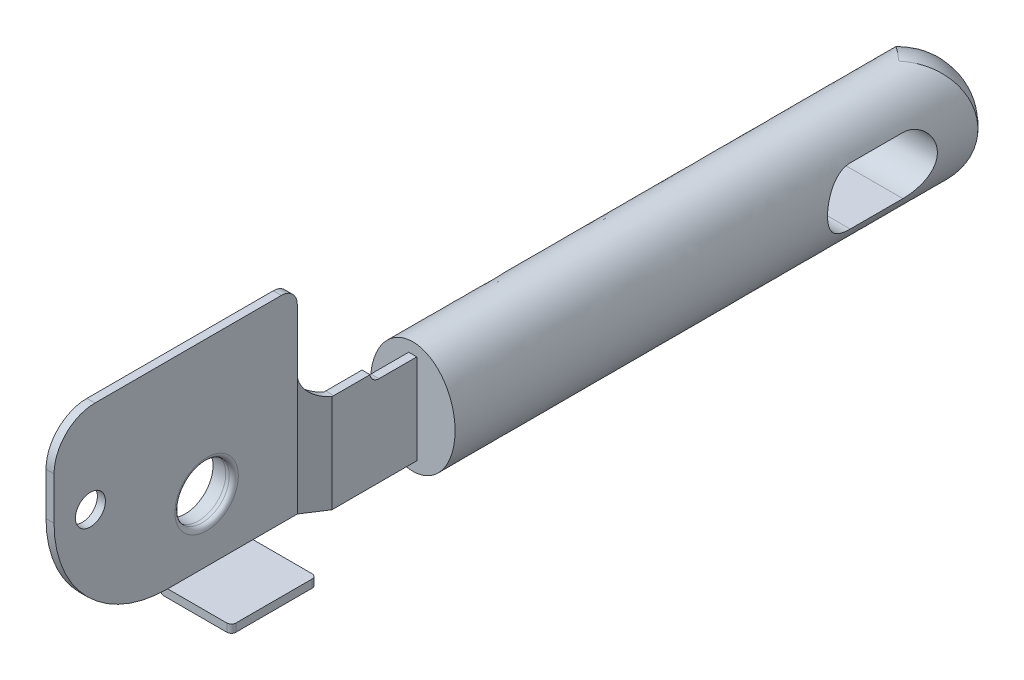
SolidWorks part; units mm, degrees
material "1060 Alloy"
ref_plane "Front Plane" through (0, 0, 0) normal (0, 0, 1) x (1, 0, 0)
ref_plane "Top Plane" through (0, 0, 0) normal (0, 1, 0) x (1, 0, 0)
ref_plane "Right Plane" through (0, 0, 0) normal (1, 0, 0) x (0, 0, -1)
sketch "Sketch1" plane through (0, 0, 0) normal (0, 0, 1) x (1, 0, 0)
  ellipse E0 centre (0, 0) end of major axis (0, 12.335) minor radius 9.31
  dimension "D1" = 24.67
  dimension "D2" = 18.62
extrude "Boss-Extrude1" add sketch "Sketch1" against normal blind 106.91
sketch "Sketch2" plane through (0, 0, 0) normal (1, 0, 0) x (0, 0, -1)
  line L0 (106.91, 0) -> (119.245, 0)
  line L2 (106.91, 12.335) -> (106.91, 0)
  arc A0 (106.91, 12.335) -> (119.245, 0) centre (106.91, 0) cw
revolve "Revolve1" add sketch "Sketch2" angle 360 about L0
sketch "Sketch4" plane through (0, 0, -106.91) normal (0, 0, 1) x (1, 0, 0)
  circle A0 centre (0, 0) radius 15.9447
  ellipse E0 centre (0, 0) end of major axis (0, 12.335) minor radius 9.31
  ellipse E1 centre (0, 0) end of major axis (0, 12.335) minor radius 9.31 construction
extrude "Cut-Extrude15" cut sketch "Sketch4" against normal blind 106.91
sketch "Sketch6" plane through (0, 0, 0) normal (1, 0, 0) x (0, 0, -1)
  line L0 (0, -9.9) -> (0, 9.9)
  line L1 (0, 12.335) -> (0, -12.335) construction
  line L2 (0, 9.9) -> (-8.296, 9.9)
  line L3 (-10.28, 11.6477) -> (-18.64, 11.6477)
  line L4 (-18.64, 11.6477) -> (-18.6436, -9.9)
  line L5 (-18.6436, -9.9) -> (0, -9.9)
  arc A0 (-8.296, 9.9) -> (-10.28, 11.6477) centre (-8.296, 11.9) cw
  point P4 (0, 0)
  dimension "D6" = 2
  dimension "D1" = 19.8
  dimension "D2" = 18.6436
  dimension "D4" = 8.36
  dimension "D5" = 18.64
extrude "Boss-Extrude2" add sketch "Sketch6" along normal mid plane 1.77
ref_plane "Plane2" through (0, 11.6446, -0.0019) normal (0, 1, -0.0002) x (-1, 0, 0)
sketch "Sketch9" plane through (0, 11.6446, -0.0019) normal (0, 1, -0.0002) x (-1, 0, 0)
  line L0 (-0.885, 18.6419) -> (0.885, 18.6419)
  line L1 (-0.885, 18.6419) -> (2.115, 23.2867)
  line L2 (0.885, 18.6419) -> (3.885, 23.2867)
  line L3 (2.115, 23.2867) -> (3.885, 23.2867)
  dimension "D1" = 3
extrude "Boss-Extrude6" add sketch "Sketch9" against normal up to surface (21.5477 mm away) up to face at (0, -9.9, 9.3218)
sketch "Sketch10" plane through (0, 11.6446, -0.0019) normal (0, 1, -0.0002) x (-1, 0, 0)
  line L1 (2.115, 23.2867) -> (3.885, 23.2867)
  line L2 (2.115, 23.2867) -> (2.115, 76.7867)
  line L3 (2.115, 76.7867) -> (3.885, 76.7867)
  line L4 (3.885, 23.2867) -> (3.885, 76.7867)
  dimension "D1" = 53.5
extrude "Boss-Extrude8" add sketch "Sketch10" against normal up to surface (21.5485 mm away) separate body up to face at (-1, -9.9, 13.9773)
sketch "Sketch11" plane through (0, 11.6446, -0.0019) normal (0, 1, -0.0002) x (-1, 0, 0)
  line L0 (2.115, 23.2867) -> (3.885, 23.2867)
  line L1 (2.115, 23.2867) -> (2.115, 76.7867)
  line L2 (3.885, 23.2867) -> (3.885, 76.7867)
  line L3 (2.115, 76.7867) -> (3.885, 76.7867)
extrude "Boss-Extrude11" add sketch "Sketch11" along normal offset from surface (21.8515 mm away) 43.4
fillet "Fillet1" radius 9 1 edges at (-3, 33.5, 76.7811)
fillet "Fillet3" radius 25 1 edges at (-3, -9.9, 76.7883)
sketch "Sketch13" plane through (0, -9.9, 0) normal (0, -1, 0) x (1, 0, 0)
  line L0 (-3.885, 51.7841) -> (-3.885, 23.2883) construction
  line L1 (-3.885, 33.02) -> (-2.115, 33.02)
  line L2 (-3.885, 33.02) -> (-3.885, 51.7841)
  line L3 (-3.885, 51.7841) -> (-2.115, 51.7841)
  line L4 (-2.115, 33.02) -> (-2.115, 51.7841)
  line L5 (-2.115, 23.2883) -> (-2.115, 51.7841) construction
  line L6 (0.885, 0) -> (-0.885, 0) construction
  dimension "D1" = 33.02
extrude "Boss-Extrude13" add sketch "Sketch13" along normal blind 1.77
sketch "Sketch14" plane through (-2.115, 0, 0) normal (1, 0, 0) x (0, 0, -1)
  line L0 (-51.7841, -9.9) -> (-51.7841, -11.67)
  line L1 (-51.7841, -9.9) -> (-33.02, -9.9)
  line L2 (-51.7841, -11.67) -> (-33.02, -11.67)
  line L3 (-33.02, -9.9) -> (-33.02, -11.67)
  line L4 (-51.7841, -11.67) -> (-51.7841, -9.9) construction
extrude "Boss-Extrude14" add sketch "Sketch14" along normal blind 14
fillet "Fillet4" radius 3.5 1 edges at (-3, 33.5, 23.2811)
sketch "Sketch15" plane through (-2.115, 0, 0) normal (1, 0, 0) x (0, 0, -1)
  line L1 (-33.02, -9.9) -> (-51.7841, -9.9) construction
  line L2 (0, 12.335) -> (0, -12.335) construction
  circle A0 centre (-43.2271, 3.87) radius 5.9817
  dimension "D2" = 11.9634
  dimension "D1" = 43.2271
  dimension "D3" = 13.77
extrude "Cut-Extrude16" cut sketch "Sketch15" against normal blind 14
sketch "Sketch16" plane through (-3.885, 0, 0) normal (-1, 0, 0) x (0, 0, 1)
  circle A0 centre (43.2271, 3.87) radius 7.57
  circle A1 centre (43.2271, 3.87) radius 6.11
  dimension "D1" = 15.14
extrude "Boss-Extrude15" add sketch "Sketch16" along normal offset from surface (2.93 mm away) 4.7 up to face at (-2.115, 3.87, 37.2454)
fillet "Fillet5" radius 1 1 edges at (-3.885, -11.67, 42.4021)
fillet "Fillet6" radius 1 1 edges at (11.885, -10.785, 33.02)
fillet "Fillet7" radius 1 1 edges at (11.885, -10.785, 51.7841)
fillet "Fillet8" radius 1 1 edges at (-2.115, 3.87, 37.2454)
sketch "Sketch17" plane through (0, 0, 0) normal (1, 0, 0) x (0, 0, -1)
  line L0 (99.79, 0) -> (88.22, 0) construction
  line L1 (99.79, -6.295) -> (88.22, -6.295)
  line L2 (99.79, 6.295) -> (88.22, 6.295)
  line L3 (119.245, 0) -> (109.6213, 0) construction
  arc A0 (99.79, -6.295) -> (99.79, 6.295) centre (99.79, 0) ccw
  arc A1 (88.22, 6.295) -> (88.22, -6.295) centre (88.22, 0) ccw
  arc A2 (106.91, -12.335) -> (106.91, 12.335) centre (106.91, 0) ccw construction
  point P3 (94.005, 0)
  point P13 (106.085, 0)
  point P14 (81.925, 0)
  dimension "D1" = 13.16
  dimension "D2" = 12.59
  dimension "D3" = 24.16
extrude "Cut-Extrude17" cut sketch "Sketch17" against normal mid plane 25.7
sketch "Sketch18" plane through (-2.115, 0, 0) normal (1, 0, 0) x (0, 0, -1)
  line L0 (-67.7826, 33.5) -> (-26.7816, 33.5) construction
  line L1 (-76.7841, 15.1042) -> (-76.7826, 24.5015) construction
  circle A0 centre (-68.7844, 13.7) radius 3.302
  dimension "D3" = 6.604
  dimension "D1" = 19.8
  dimension "D2" = 8
extrude "Cut-Extrude18" cut sketch "Sketch18" against normal blind 25.7
fillet "Fillet10" radius 5.0038 1 edges at (-3, 11.6485, 23.2847)
